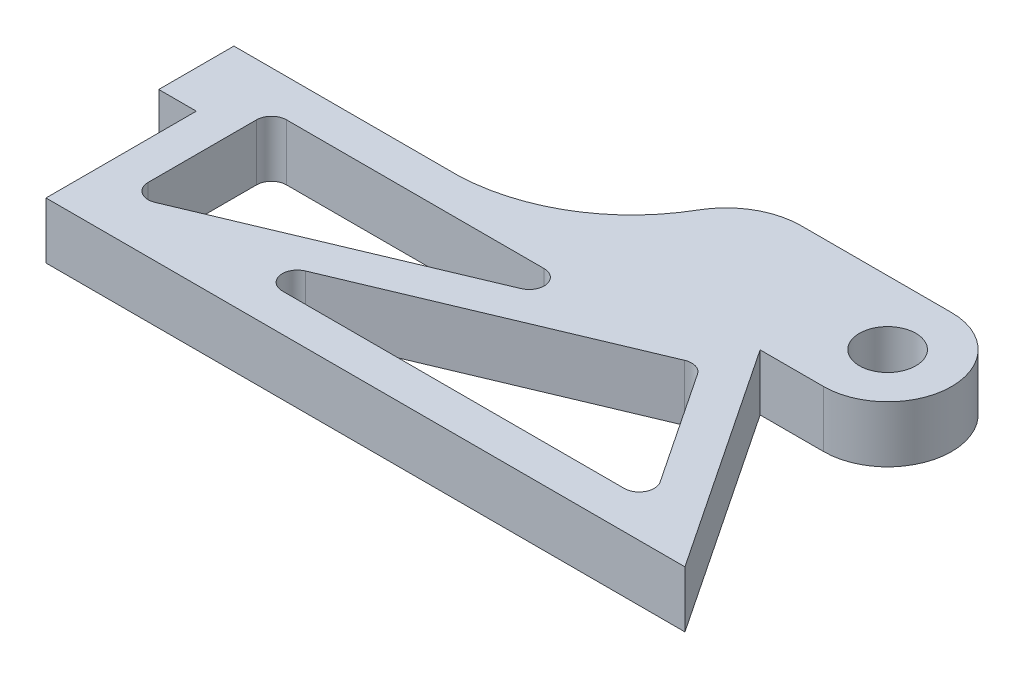
SolidWorks part; units mm, degrees
material "UHMW"
ref_plane "Front Plane" through (0, 0, 0) normal (0, 0, 1) x (1, 0, 0)
ref_plane "Top Plane" through (0, 0, 0) normal (0, 1, 0) x (1, 0, 0)
ref_plane "Right Plane" through (0, 0, 0) normal (1, 0, 0) x (0, 0, -1)
other "Bounding Box"
ref_plane "Default Plane" through (-8.9266, -12.7485, 0) normal (-0.1736, 0.9848, 0) x (0.9848, 0.1736, 0)
sketch "Sketch1" plane through (0, 0, 0) normal (0, 1, 0) x (1, 0, 0)
  line L0 (0, 0) -> (38.1, 0)
  line L1 (88.9, 0) -> (114.3, -38.1)
  line L2 (114.3, -38.1) -> (6.35, -38.1)
  line L3 (6.35, -38.1) -> (6.35, -12.7)
  line L4 (6.35, -12.7) -> (0, -12.7)
  line L5 (0, -12.7) -> (0, 0)
  line L6 (99.6289, 0) -> (88.9, 0)
  line L9 (99.6289, 21.632) -> (74.2289, 21.632)
  line L13 (85.9934, -7.0877) -> (102.4349, -31.75)
  line L14 (102.4349, -31.75) -> (27.3303, -31.75)
  line L15 (12.7, -31.0123) -> (12.7, -6.35)
  line L16 (12.7, -6.35) -> (71.363, -6.35)
  line L17 (12.7, -31.0123) -> (71.363, -6.35)
  line L18 (85.9934, -7.0877) -> (27.3303, -31.75)
  circle A0 centre (99.6289, 10.816) radius 4.7625
  arc A1 (99.6289, 21.632) -> (99.6289, 0) centre (99.6289, 10.816) cw
  arc A4 (74.2289, 21.632) -> (63.2185, 15.2614) centre (74.2289, 8.932) ccw
  arc A5 (63.2185, 15.2614) -> (38.1, 0) centre (36.7936, 30.452) cw
  point P16 (48.8289, 0)
  point P21 (61.0162, 15.3252)
  point P26 (66.4366, 15.2522)
  point P27 (63.0415, 15.259)
  point P28 (0, 0)
  dimension "D7" = 50.8
  dimension "D8" = 9.525
  dimension "D9" = 10.7289
  dimension "D6" = 10.816
  dimension "D10" = 30.48
  dimension "D16" = 12.7
  dimension "D1" = 6.35
  dimension "D2" = 38.1
  dimension "D3" = 107.95
  dimension "D4" = 88.9
  dimension "D5" = 12.7
  dimension "D11" = 6.35
  dimension "D12" = 6.35
  dimension "D13" = 6.35
  dimension "D14" = 6.35
  dimension "D15" = 6.35
  dimension "D17" = 38.1
  dimension "D18" = 25.4
extrude "Boss-Extrude1" add sketch "Sketch1" along normal blind 9.525
fillet "Fillet6" radius 2.54 6 edges at (102.4349, 4.7625, 31.75) (85.9934, 4.7625, 7.0877) (27.3303, 4.7625, 31.75) (12.7, 4.7625, 31.0123) (12.7, 4.7625, 6.35) (71.363, 4.7625, 6.35)
